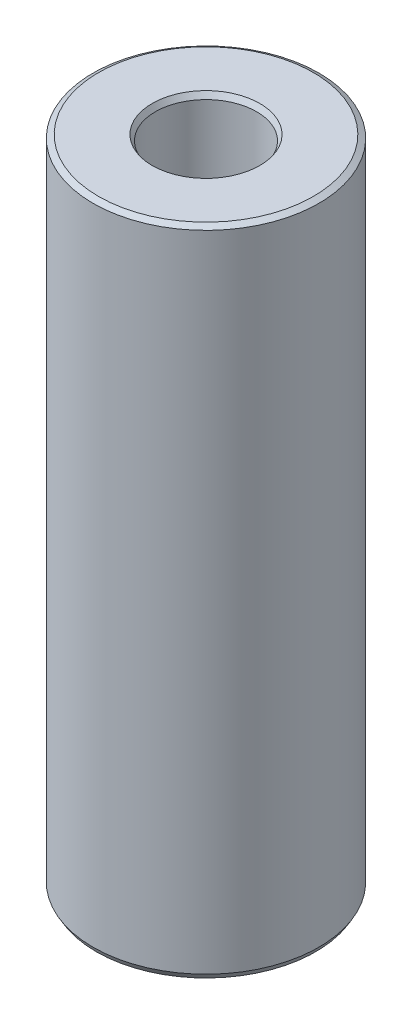
SolidWorks part; units mm, degrees
ref_plane "Front Plane" through (0, 0, 0) normal (0, 0, 1) x (1, 0, 0)
ref_plane "Top Plane" through (0, 0, 0) normal (0, 1, 0) x (1, 0, 0)
ref_plane "Right Plane" through (0, 0, 0) normal (1, 0, 0) x (0, 0, -1)
sketch "Sketch1" plane through (0, 0, 0) normal (0, 1, 0) x (1, 0, 0)
  circle A0 centre (0, 0) radius 40
  dimension "SLEEVE_OD" = 80
extrude "Boss-Extrude1" add sketch "Sketch1" along normal blind 231.2776
sketch "Sketch2" plane through (0, 0, 0) normal (0, 1, 0) x (1, 0, 0)
  circle A0 centre (0, 0) radius 17.9257
  dimension "BORE_D" = 35.8513
extrude "Cut-Extrude1" cut sketch "Sketch2" along normal through all
chamfer "Chamfer1" distance 1.1324 angle 60 4 edges at (0, 231.2776, 17.9257) (0, 0, 17.9257) (0, 0, 40) (0, 231.2776, 40) first distance on face at (0, 231.2776, 17.9257) first distance on face at (0, 0, 17.9257) first distance on face at (0, 231.2776, 40)
